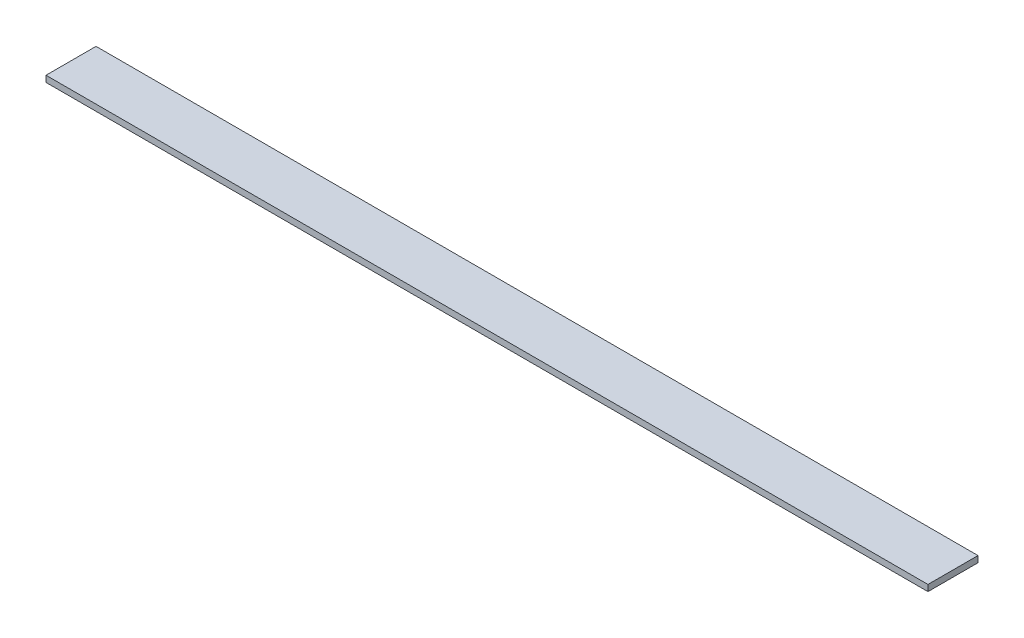
SolidWorks part; units mm, degrees
material "6061-T6 (SS)"
ref_plane "Front" through (0, 0, 0) normal (0, 0, 1) x (1, 0, 0)
ref_plane "Top" through (0, 0, 0) normal (0, 1, 0) x (1, 0, 0)
ref_plane "Right" through (0, 0, 0) normal (1, 0, 0) x (0, 0, -1)
sketch "Sketch1" plane through (0, 0, 0) normal (0, 1, 0) x (1, 0, 0)
  line L1 (-223.8248, -12.7) -> (223.8248, -12.7)
  line L2 (-223.8248, -12.7) -> (-223.8248, 12.7)
  line L3 (-223.8248, 12.7) -> (223.8248, 12.7)
  line L4 (223.8248, -12.7) -> (223.8248, 12.7)
  line L5 (-223.8248, -12.7) -> (223.8248, 12.7) construction
  line L6 (-223.8248, 12.7) -> (223.8248, -12.7) construction
  point P0 (0, 0)
  dimension "D1" = 447.6496
  dimension "D2" = 25.4
base flange "Base-Flange1" sketch "Sketch1" thickness 3.175 reverse thickness direction no parameters "D1"=1.524
sketch "Bend-Lines1" plane through (0, 0, 0) normal (0, 1, 0) x (1, 0, 0)
sketch "Bounding-Box1" plane through (0, 0, 0) normal (0, 1, 0) x (1, 0, 0)
sheet metal parameters "Sheet-Metal8" thickness 3.175 parameters "D1"=1.524
flat pattern "Flat-Pattern8" [suppressed]
sketch "Bend-Lines2" plane through (0, 0, 0) normal (0, 1, 0) x (1, 0, 0)
sketch "Bounding-Box2" [suppressed] plane through (0, 0, 0) normal (0, 1, 0) x (1, 0, 0)
